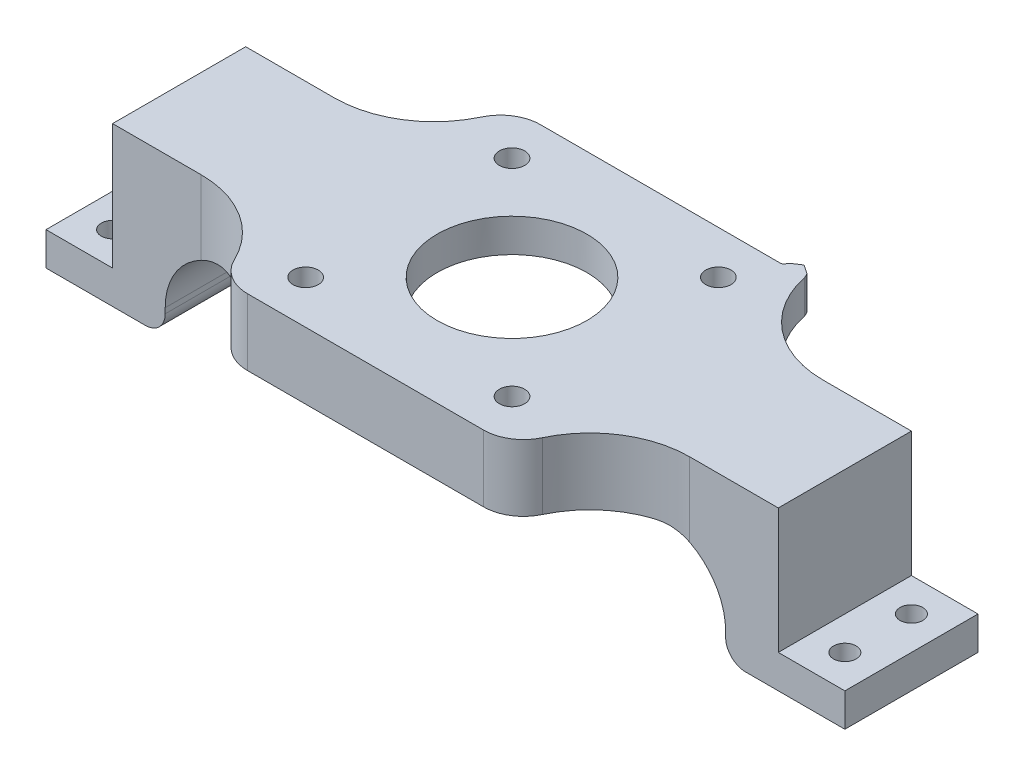
SolidWorks part; units mm, degrees
ref_plane "Ebene vorne" through (0, 0, 0) normal (0, 0, 1) x (1, 0, 0)
ref_plane "Ebene oben" through (0, 0, 0) normal (0, 1, 0) x (1, 0, 0)
ref_plane "Ebene rechts" through (0, 0, 0) normal (1, 0, 0) x (0, 0, -1)
sketch "Skizze1" plane through (0, 0, 0) normal (0, 1, 0) x (1, 0, 0)
  line L0 (-60, -4.8) -> (-22, -4.8)
  line L1 (60, -4.8) -> (60, 15.2)
  line L2 (60, 15.2) -> (22, 15.2)
  line L3 (0, 10.4) -> (0, 0) construction
  line L4 (-60, -4.8) -> (-60, 15.2)
  line L5 (22, -4.8) -> (60, -4.8)
  line L6 (-22, 15.2) -> (-22, 27.2)
  line L7 (-15.5, -10.3) -> (15.5, -10.3) construction
  line L8 (-15.5, -10.3) -> (-15.5, 20.7) construction
  line L9 (-15.5, 20.7) -> (15.5, 20.7) construction
  line L10 (15.5, -10.3) -> (15.5, 20.7) construction
  line L11 (-15.5, -10.3) -> (15.5, 20.7) construction
  line L12 (-15.5, 20.7) -> (15.5, -10.3) construction
  line L13 (-22, -16.8) -> (22, -16.8)
  line L14 (-22, -16.8) -> (-22, -4.8)
  line L15 (-22, 27.2) -> (0, 27.2)
  line L16 (22, -16.8) -> (22, -4.8)
  line L17 (-22, -16.8) -> (22, 27.2) construction
  line L18 (-22, 27.2) -> (22, -16.8) construction
  line L19 (22, 15.2) -> (22, 27.2)
  line L20 (-22, 15.2) -> (-60, 15.2)
  line L21 (0, 5.2) -> (-66.3854, 5.2) construction
  line L22 (0, 5.2) -> (0, 50.559) construction
  line L23 (0, 27.2) -> (22, 27.2)
  point P7 (0, 5.2)
  point P8 (0, 5.2)
  point P11 (-60, 5.2)
  dimension "D3" = 31
  dimension "D1" = 120
  dimension "D2" = 20
  dimension "D4" = 44
  dimension "D5" = 44
extrude "Aufsatz-Linear austragen1" add sketch "Skizze1" along normal blind 10
sketch "Skizze4" plane through (-60, 0, 0) normal (1, 0, 0) x (0, 0, -1)
  line L0 (-4.8, 10) -> (15.2, 10)
  line L1 (15.2, 10) -> (15.2, 9.0736)
  line L2 (15.2, 10) -> (15.2, 0) construction
  line L3 (-4.8, 10) -> (-4.8, 5.2708)
  line L4 (-4.8, 10) -> (-4.8, 0) construction
  arc A1 (-4.8, 5.2708) -> (15.2, 9.0736) centre (58.0172, -270.6068) cw
extrude "Schnitt-Linear austragen2" [suppressed] cut sketch "Skizze4" along normal blind 10
fillet "Verrundung1" [suppressed] radius 10
mirror "Spiegeln1" [suppressed] about plane through (0, 0, 0) normal (1, 0, 0)
sketch "Skizze6" plane through (0, 10, 0) normal (0, 1, 0) x (1, 0, 0)
  line L0 (0, 27.2) -> (0, -16.8) construction
  line L3 (22, 27.2) -> (-22, 27.2) construction
  line L4 (-15.5, -10.3) -> (15.5, -10.3) construction
  line L5 (-15.5, -10.3) -> (-15.5, 20.7) construction
  line L6 (-15.5, 20.7) -> (15.5, 20.7) construction
  line L7 (15.5, -10.3) -> (15.5, 20.7) construction
  line L8 (-15.5, -10.3) -> (15.5, 20.7) construction
  line L9 (-15.5, 20.7) -> (15.5, -10.3) construction
  line L10 (-22, -16.8) -> (22, -16.8) construction
  circle A0 centre (15.5, 20.7) radius 1.9
  circle A1 centre (15.5, -10.3) radius 1.9
  circle A2 centre (-15.5, -10.3) radius 1.9
  circle A3 centre (-15.5, 20.7) radius 1.9
  circle A4 centre (0, 5.2) radius 11.25
  point P6 (0, 5.2)
  dimension "D2" = 3.8
  dimension "D3" = 22.5
  dimension "D1" = 31
extrude "Schnitt-Linear austragen4" cut sketch "Skizze6" against normal through all
sketch "Skizze7" plane through (-22, 0, 0) normal (-1, 0, 0) x (0, 0, 1)
  line L0 (-36.0808, 5) -> (-15.2, 5)
  line L2 (-15.2, 10) -> (-15.2, 0) construction
  line L3 (-15.2, 5) -> (-15.2, 0)
  line L4 (-15.2, 0) -> (-36.0808, 0)
  line L6 (-36.0808, 5) -> (-36.0808, 0)
extrude "Schnitt-Linear austragen5" cut sketch "Skizze7" against normal through all
fillet "Verrundung2" [suppressed] radius 10
fillet "Verrundung3" radius 15 4 edges at (-22, 7.5, -15.2) (-22, 5, 4.8) (22, 5, 4.8) (22, 7.5, -15.2)
fillet "Verrundung4" [suppressed] radius 22
sketch "Skizze8" plane through (0, 0, -15.2) normal (0, 0, -1) x (-1, 0, 0)
  line L6 (-60, 0) -> (-50, 0)
  line L8 (-50, 0) -> (-50, 10)
  line L10 (-50, 10) -> (-60, 10)
  line L11 (-60, 10) -> (-60, 0)
  line L12 (0, 0) -> (0, 15.1362) construction
  line L13 (-11.25, 0) -> (11.25, 0) construction
  line L14 (60, 10) -> (60, 0)
  line L15 (50, 10) -> (60, 10)
  line L16 (50, 0) -> (50, 10)
  line L17 (60, 0) -> (50, 0)
  dimension "D1" = 10
extrude "Schnitt-Linear austragen6" cut sketch "Skizze8" against normal through all and the other way through all
sketch "Skizze12" plane through (0, 0, -15.2) normal (0, 0, -1) x (-1, 0, 0)
  line L0 (-50, 0) -> (-50, -8.7956)
  line L1 (-50, -8.7956) -> (-60, -8.7956)
  line L2 (-60, -8.7956) -> (-60, -13.7956)
  line L3 (-60, -13.7956) -> (-42.0937, -13.7956)
  line L4 (-42.0937, -13.7956) -> (-42.0937, 0)
  line L5 (-50, 0) -> (-5.1539, 0) construction
  line L6 (0, 0) -> (0, -22.5067) construction
  line L7 (-50, 0) -> (-42.0937, 0)
  line L8 (50, 0) -> (42.0937, 0)
  line L9 (42.0937, -13.7956) -> (42.0937, 0)
  line L10 (60, -13.7956) -> (42.0937, -13.7956)
  line L11 (60, -8.7956) -> (60, -13.7956)
  line L12 (50, -8.7956) -> (60, -8.7956)
  line L13 (50, 0) -> (50, -8.7956)
  dimension "D1" = 5
extrude "Aufsatz-Linear austragen4" add sketch "Skizze12" against normal up to surface (20 mm away) up to face at (43.3485, 5, 4.8)
sketch "Skizze9" [suppressed] plane through (0, 5, 0) normal (0, 1, 0) x (-1, 0, 0)
  line L0 (60, -5.2) -> (50, -5.2) construction
  line L1 (60, 4.8) -> (60, -15.2) construction
  line L2 (50, 4.8) -> (50, -15.2) construction
  line L3 (55, -5.2) -> (55, 4.8) construction
  line L4 (60, 4.8) -> (50, 4.8) construction
  line L5 (0, 0) -> (0, -8.3592) construction
  circle A0 centre (55, -0.2) radius 1.7
  circle A1 centre (55, -10.2) radius 1.7
  circle A2 centre (-55, -10.2) radius 1.7
  circle A3 centre (-55, -0.2) radius 1.7
  dimension "D1" = 3.4
extrude "Schnitt-Linear austragen7" [suppressed] cut sketch "Skizze9" against normal blind 10
sketch "Skizze10" plane through (0, 10, 0) normal (0, 1, 0) x (1, 0, 0)
  line L0 (-22, 27.2) -> (-20.3604, 30.3072)
  line L1 (-20.3604, 30.3072) -> (-20.3604, 27.2) construction
  line L2 (22, 27.2) -> (-22, 27.2) construction
  line L3 (-18.7207, 27.2) -> (-20.3604, 30.3072)
  line L4 (-18.7207, 27.2) -> (-22, 27.2)
extrude "Aufsatz-Linear austragen2" [suppressed] add sketch "Skizze10" against normal blind 5
sketch "Skizze11" plane through (0, 10, 0) normal (0, 1, 0) x (1, 0, 0)
  line L0 (23.7415, 47.7995) -> (24.8232, 40.4162) construction
  line L1 (24.8232, 40.4162) -> (25.9159, 32.9579) construction
  line L2 (25.9159, 32.9579) -> (25.9159, 14.8182) construction
  line L3 (25.9159, 32.2165) -> (27.5941, 30.2165)
  line L4 (25.9159, 32.2165) -> (24.2377, 30.2165)
  line L5 (24.2377, 30.2165) -> (22, 27.2)
  line L6 (27.5941, 30.2165) -> (28.9419, 17.3602)
  line L7 (28.9419, 17.3602) -> (24.0809, 17.5461)
  line L8 (24.0809, 17.5461) -> (21.4223, 25.8471)
  line L9 (21.4223, 25.8471) -> (22, 27.2)
  arc A0 (-127.1113, 338.6796) -> (126.7578, 338.6796) centre (-0.1768, 211.0567) ccw construction
  arc A1 (22, 27.2) -> (36.6969, 15.2) centre (36.6969, 30.2) ccw construction
  dimension "D1" = 2
  dimension "D2" = 40
extrude "Aufsatz-Linear austragen3" [suppressed] add sketch "Skizze11" against normal up to vertex up to point (22, 5, -27.2)
fillet "Verrundung5" [suppressed] radius 3
sketch "Skizze13" plane through (0, 5, 0) normal (0, -1, 0) x (1, 0, 0)
  line L0 (-25.9463, -32.0214) -> (-25.9463, -16.8451) construction
  line L1 (-25.9463, -32.0214) -> (-28.1878, -29.3)
  line L2 (-25.9463, -32.0214) -> (-23.7048, -29.3)
  line L3 (-22, -27.2) -> (-23.7048, -29.3)
  line L4 (-28.1878, -29.3) -> (-30.1903, -16.6847)
  line L5 (-22, -27.2) -> (-20.315, -24.4193)
  line L6 (-20.315, -24.4193) -> (-22.3184, -19.0601)
  line L7 (-22.3184, -19.0601) -> (-28.1878, -15.5036)
  line L8 (-28.1878, -15.5036) -> (-30.1903, -16.6847)
  arc A0 (-22, -27.2) -> (-36.6969, -15.2) centre (-36.6969, -30.2) ccw construction
extrude "Aufsatz-Linear austragen5" [suppressed] add sketch "Skizze13" against normal up to surface (5 mm away) up to face at (0, 10, -5.2)
fillet "Verrundung6" [suppressed] radius 5
fillet "Verrundung7" radius 10 2 edges at (42.0937, 0, -5.2) (-42.0937, 0, -5.2)
fillet "Verrundung8" radius 3 2 edges at (-42.0937, -13.7956, -5.2) (42.0937, -13.7956, -5.2)
sketch "Skizze16" plane through (0, -13.7956, 0) normal (0, -1, 0) x (1, 0, 0)
  line L0 (-60, -5.2) -> (-50, -5.2) construction
  line L1 (-60, 4.8) -> (-60, -15.2) construction
  line L2 (-55, -5.2) -> (-55, -15.2) construction
  line L3 (-45.0937, -15.2) -> (-60, -15.2) construction
  line L4 (0, 0) -> (0, -35.9301) construction
  circle A0 centre (-55, -10.2) radius 1.7
  circle A1 centre (-55, -0.2) radius 1.7
  circle A2 centre (55, -0.2) radius 1.7
  circle A3 centre (55, -10.2) radius 1.7
  dimension "D2" = 3.4
  dimension "D1" = 10
extrude "Schnitt-Linear austragen8" cut sketch "Skizze16" against normal blind 10
sketch "Skizze17" plane through (0, 5, 0) normal (0, -1, 0) x (1, 0, 0)
  line L0 (20.3233, -27.2) -> (20.3233, -31.6412) construction
  line L1 (22, -27.2) -> (-22, -27.2) construction
  line L2 (20.3233, -28.736) -> (21.6811, -27.8415)
  line L3 (21.6811, -27.8415) -> (22, -27.2)
  line L4 (20.3233, -28.736) -> (18.9655, -27.8415)
  line L5 (18.9655, -27.8415) -> (18.6466, -27.2)
  line M12 (-22, -27.2) -> (22, -27.2)
extrude "Aufsatz-Linear austragen6" add sketch "Skizze17" against normal up to vertex (5 mm away) contours L0 L2 L3 M12 | L0 L5 L4 M12 region at (20.9661, 5, -27.7516) region at (19.6805, 5, -27.7516) up to point (22, 10, -27.2)
fillet "Verrundung9" radius 0.5 4 edges at (18.9655, 7.5, -27.8415) (21.6811, 7.5, -27.8415) (22, 7.5, -27.2) (18.6466, 7.5, -27.2)
chamfer "Fase1" distance 28 angle 35 2 edges at (-5.1539, 2.5, -15.2) (5.1539, 2.5, -15.2) first distance on face at (-38.8772, -2.8774, -15.2) first distance on face at (38.8772, -2.8774, -15.2)
fillet "Verrundung10" radius 10 4 edges at (-8.7186, 2.5, 1.9098) (8.7186, 2.5, 1.9098) (-33.1539, 2.4718, -15.2) (33.1539, 2.4718, -15.2)
fillet "Verrundung11" radius 6 3 edges at (22, 5, 16.8) (-22, 5, 16.8) (-22, 7.5, -27.2)
